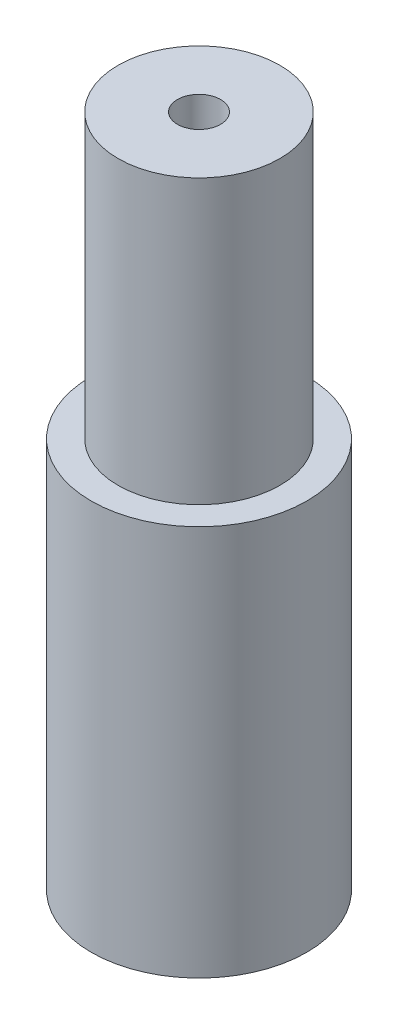
SolidWorks part; units mm, degrees
ref_plane "Front Plane" through (0, 0, 0) normal (0, 0, 1) x (1, 0, 0)
ref_plane "Top Plane" through (0, 0, 0) normal (0, 1, 0) x (1, 0, 0)
ref_plane "Right Plane" through (0, 0, 0) normal (1, 0, 0) x (0, 0, -1)
sketch "Sketch1" plane through (0, 0, 0) normal (0, 1, 0) x (1, 0, 0)
  circle A0 centre (0, 0) radius 4
extrude "Boss-Extrude1" add sketch "Sketch1" along normal blind 14.5
sketch "Sketch2" plane through (0, 14.5, 0) normal (0, 1, 0) x (1, 0, 0)
  circle A0 centre (0, 0) radius 3
extrude "Boss-Extrude2" add sketch "Sketch2" along normal blind 10.5
sketch "Sketch3" plane through (0, 25, 0) normal (0, 1, 0) x (1, 0, 0)
  circle A0 centre (0, 0) radius 0.8
extrude "Cut-Extrude1" cut sketch "Sketch3" against normal blind 25
ref_axis "Axis1" through (0, -5.5757, 0) along (0, 1, 0)
sketch "Sketch4" plane through (0, 14.5, 0) normal (0, 1, 0) x (1, 0, 0)
  circle A0 centre (0, 0) radius 5
